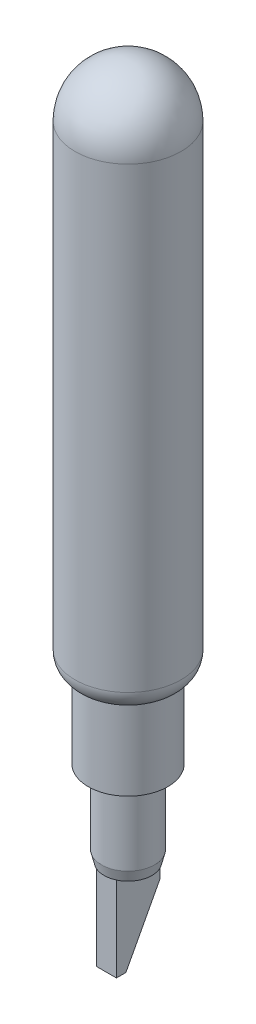
SolidWorks part; units mm, degrees
ref_plane "Alzado" through (0, 0, 0) normal (0, 0, 1) x (1, 0, 0)
ref_plane "Planta" through (0, 0, 0) normal (0, 1, 0) x (1, 0, 0)
ref_plane "Vista lateral" through (0, 0, 0) normal (1, 0, 0) x (0, 0, -1)
sketch "Croquis1" plane through (0, 0, 0) normal (0, 1, 0) x (1, 0, 0)
  circle A0 centre (0, 0) radius 10
  dimension "D1" = 20
extrude "Saliente-Extruir1" add sketch "Croquis1" along normal blind 100
sketch "Croquis2" plane through (0, 0, 0) normal (0, -1, 0) x (1, 0, 0)
  circle A0 centre (0, 0) radius 7.5
  dimension "D1" = 15
extrude "Saliente-Extruir2" add sketch "Croquis2" along normal blind 15
sketch "Croquis3" plane through (0, -15, 0) normal (0, -1, 0) x (1, 0, 0)
  circle A0 centre (0, 0) radius 5
  dimension "D1" = 10
extrude "Saliente-Extruir3" add sketch "Croquis3" along normal blind 16
fillet "Redondeo1" radius 4 1 edges at (0, 0, 10)
chamfer "Chaflán1" distance 1.99 angle 14 1 edges at (0, -31, -5) first distance on face at (0, -31, -5)
sketch "Croquis4" plane through (0, -31, 0) normal (0, -1, 0) x (1, 0, 0)
  line L1 (-1.8968, -4.0849) -> (1.8968, -4.0849)
  line L2 (-1.8968, -4.0849) -> (-1.8968, 4.0849)
  line L3 (-1.8968, 4.0849) -> (1.8968, 4.0849)
  line L4 (1.8968, -4.0849) -> (1.8968, 4.0849)
  line L5 (-1.8968, -4.0849) -> (1.8968, 4.0849) construction
  line L6 (-1.8968, 4.0849) -> (1.8968, -4.0849) construction
  circle A0 centre (0, 0) radius 4.5038 construction
  point P0 (0, 0)
extrude "Saliente-Extruir4" add sketch "Croquis4" along normal blind 16
chamfer "Chaflán2" distance 12 angle 28 1 edges at (0, -47, -4.0849) first distance on face at (0, -39, -4.0849)
fillet "Redondeo2" radius 10 1 edges at (0, 100, 10)
